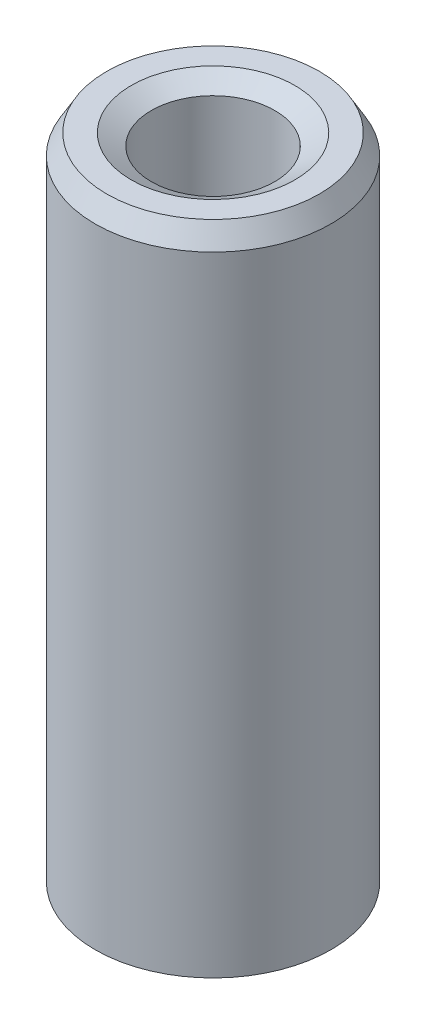
SolidWorks part; units mm, degrees
ref_plane "Front Plane" through (0, 0, 0) normal (0, 0, 1) x (1, 0, 0)
ref_plane "Top Plane" through (0, 0, 0) normal (0, 1, 0) x (1, 0, 0)
ref_plane "Right Plane" through (0, 0, 0) normal (1, 0, 0) x (0, 0, -1)
sketch "Sketch1" plane through (0, 0, 0) normal (0, 1, 0) x (1, 0, 0)
  circle A0 centre (0, 0) radius 15
  dimension "SLEEVE_OD" = 30
extrude "Boss-Extrude1" add sketch "Sketch1" along normal blind 84.0063
sketch "Sketch2" plane through (0, 0, 0) normal (0, 1, 0) x (1, 0, 0)
  circle A0 centre (0, 0) radius 7.8544
  dimension "BORE_D" = 15.7089
extrude "Cut-Extrude1" cut sketch "Sketch2" along normal through all
chamfer "Chamfer1" distance 2.5572 angle 30 4 edges at (0, 84.0063, 7.8544) (0, 0, 7.8544) (0, 0, 15) (0, 84.0063, 15) first distance on face at (0, 84.0063, 7.8544) first distance on face at (0, 0, 7.8544) first distance on face at (0, 84.0063, 15)
